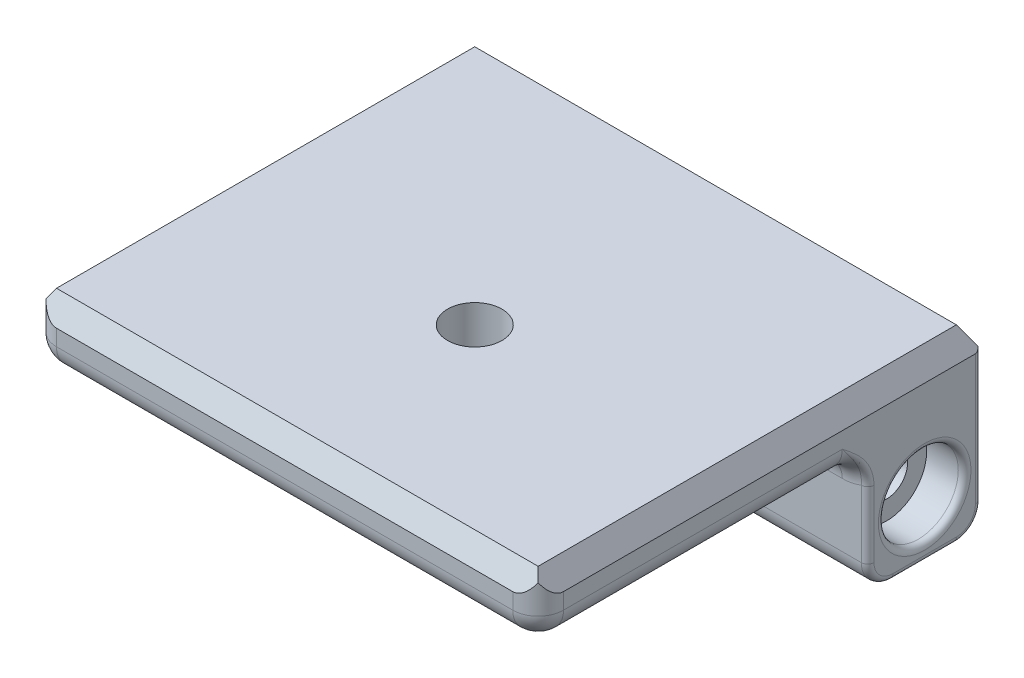
SolidWorks part; units mm, degrees
ref_plane "Front Plane" through (0, 0, 0) normal (0, 0, 1) x (1, 0, 0)
ref_plane "Top Plane" through (0, 0, 0) normal (0, 1, 0) x (1, 0, 0)
ref_plane "Right Plane" through (0, 0, 0) normal (1, 0, 0) x (0, 0, -1)
sketch "Sketch2" plane through (0, 0, 0) normal (0, 1, 0) x (1, 0, 0)
  line L1 (-20, -17.5) -> (20, -17.5)
  line L2 (-20, -17.5) -> (-20, 17.5)
  line L3 (-20, 17.5) -> (20, 17.5)
  line L4 (20, -17.5) -> (20, 17.5)
  line L5 (-20, -17.5) -> (20, 17.5) construction
  line L6 (-20, 17.5) -> (20, -17.5) construction
  circle A0 centre (0, -2.5) radius 2.15
  point P0 (0, 0)
  point P8 (0, 0)
  dimension "D4" = 4.3
  dimension "D1" = 40
  dimension "D2" = 35
  dimension "D3" = 15
extrude "Boss-Extrude1" add sketch "Sketch2" along normal blind 5
sketch "Sketch3" plane through (0, 0, 0) normal (0, -1, 0) x (1, 0, 0)
  line L1 (-20, -17.5) -> (-10, -17.5)
  line L2 (-20, -17.5) -> (-20, -8.5)
  line L3 (-20, -8.5) -> (-10, -8.5)
  line L4 (-10, -17.5) -> (-10, -8.5)
  dimension "D1" = 10
  dimension "D2" = 9
extrude "Boss-Extrude2" add sketch "Sketch3" along normal blind 9
sketch "Sketch4" plane through (-10, 0, 0) normal (1, 0, 0) x (0, 0, -1)
  line L0 (17.5, -9) -> (8.5, -9) construction
  line L1 (17.5, 0) -> (8.5, 0) construction
  circle A0 centre (13, -4.5) radius 1.65
  point P4 (13, -9)
  dimension "D2" = 3.3
  dimension "D1" = 4.5
extrude "Cut-Extrude1" cut sketch "Sketch4" against normal up to next
mirror "Mirror1" about plane through (0, 0, 0) normal (1, 0, 0) of "Cut-Extrude1", "Boss-Extrude2"
sketch "Sketch5" plane through (-20, 0, 0) normal (-1, 0, 0) x (0, 0, 1)
  circle A0 centre (-13, -4.5) radius 2.25
  dimension "D1" = 4.5
extrude "Cut-Extrude2" cut sketch "Sketch5" against normal up to next
sketch "Sketch6" plane through (20, 0, 0) normal (1, 0, 0) x (0, 0, -1)
  circle A0 centre (13, -4.5) radius 3.15
  dimension "D1" = 6.3
extrude "Cut-Extrude3" cut sketch "Sketch6" against normal blind 3
chamfer "Chamfer1" distance 1 angle 60 4 edges at (0, 5, 17.5) (-20, 5, 0) (0, 5, -17.5) (20, 5, 0) first distance on face at (0, 5, 0)
fillet "Fillet1" radius 2 4 edges at (-15, -9, -8.5) (-15, -9, -17.5) (15, -9, -17.5) (15, -9, -8.5)
fillet "Fillet2" radius 2 5 edges at (-20, 0, 4.5) (20, 0, 4.5) (0, 0, 17.5) (-20, 1.634, 17.5) (20, 1.634, 17.5)
fillet "Fillet3" radius 2 4 edges at (-19.4142, 0.5858, -8.5) (19.4142, 0.5858, -8.5) (-14, 0, -8.5) (14, 0, -8.5)
fillet "Fillet4" radius 0.5 28 edges at (-10, -3.5, -17.5) (-10, -8.4142, -16.9142) (-10, -0.5858, -7.9142) (-10, -4.5, -8.5) (-10, -8.4142, -9.0858) (10, -3.5, -17.5) (10, -8.4142, -16.9142) (10, -0.5858, -7.9142) (10, -4.5, -8.5) (10, -8.4142, -9.0858) (-20, -0.4641, -8.3213) (-20, -4.2321, -8.5) (-20, -8.4142, -9.0858) (-20, -1.866, -17.5) (-20, -8.4142, -16.9142) (20, -0.4641, -8.3213) (20, -4.2321, -8.5) (20, -8.4142, -9.0858) (20, -1.866, -17.5) (20, -8.4142, -16.9142) (-10, -9, -13) (10, -9, -13) (-20, -9, -13) (20, -9, -13) (20, -4.5, -16.15) (-10, -4.5, -10.75) (10, -4.5, -14.65) (-20, -4.5, -10.75)
fillet "Fillet5" radius 1 1 edges at (0, 0, -17.5)
